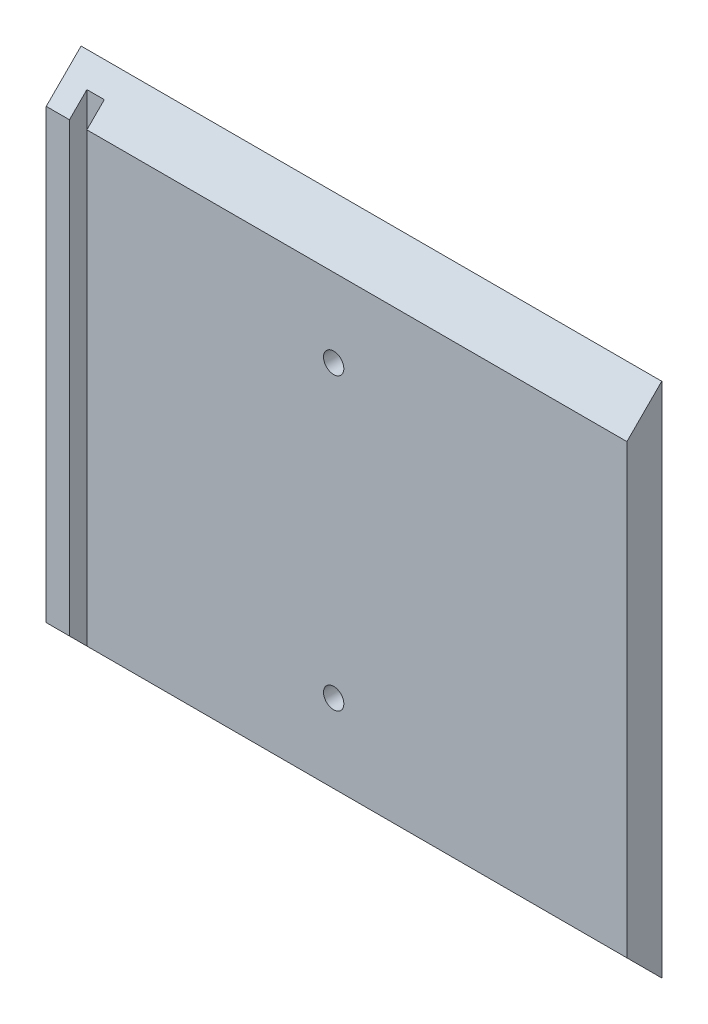
SolidWorks part; units mm, degrees
material "Maple"
ref_plane "Front Plane" through (0, 0, 0) normal (0, 0, 1) x (1, 0, 0)
ref_plane "Top Plane" through (0, 0, 0) normal (0, 1, 0) x (1, 0, 0)
ref_plane "Right Plane" through (0, 0, 0) normal (1, 0, 0) x (0, 0, -1)
sketch "Sketch1" plane through (0, 0, 0) normal (0, 0, 1) x (1, 0, 0)
  line L1 (-50, -44.5) -> (50, -44.5)
  line L2 (-50, -44.5) -> (-50, 44.5)
  line L3 (-50, 44.5) -> (50, 44.5)
  line L4 (50, -44.5) -> (50, 44.5)
  line L5 (-50, -44.5) -> (50, 44.5) construction
  line L6 (-50, 44.5) -> (50, -44.5) construction
  point P0 (0, 0)
  dimension "D1" = 100
  dimension "D2" = 89
extrude "Boss-Extrude1" add sketch "Sketch1" along normal blind 6
chamfer "Chamfer1" distance 6 angle 45 2 edges at (0, -44.5, 6) (0, 44.5, 6)
sketch "Sketch2" plane through (0, 0, 6) normal (0, 0, 1) x (1, 0, 0)
  line L0 (50, 44.5) -> (-50, 44.5) construction
  line L1 (-46, -44.5) -> (-43, -44.5)
  line L2 (-46, -44.5) -> (-46, 44.5)
  line L3 (-46, 44.5) -> (-43, 44.5)
  line L4 (-43, -44.5) -> (-43, 44.5)
  line L5 (-46, -44.5) -> (-43, 44.5) construction
  line L6 (-46, 44.5) -> (-43, -44.5) construction
  line L7 (-50, -44.5) -> (50, -44.5) construction
  line L8 (-50, 38.5) -> (-50, -38.5) construction
  point P0 (-44.5, 0)
  dimension "D1" = 3
  dimension "D2" = 4
extrude "Cut-Extrude1" cut sketch "Sketch2" against normal blind 3
sketch "Sketch3" [suppressed] plane through (0, 0, 0) normal (0, 0, -1) x (-1, 0, 0)
  line L1 (-45, -45) -> (-45, 45) construction
  circle A0 centre (-7, 20) radius 5
  dimension "D3" = 6
  dimension "D1" = 32
  dimension "D2" = 20
extrude "Cut-Extrude2" [suppressed] cut sketch "Sketch3" against normal through all
mirror "Mirror1" [suppressed] about plane through (0, 0, 0) normal (0, 1, 0)
sketch "Sketch4" plane through (0, 0, 0) normal (0, 0, -1) x (-1, 0, 0)
  line L0 (0.5, 25) -> (0.5, -25) construction
  line L1 (-50, 0) -> (50, 0) construction
  line L2 (-50, -44.5) -> (-50, 44.5) construction
  line L3 (50, 44.5) -> (50, -44.5) construction
  circle A0 centre (0.5, 25) radius 1.75
  circle A1 centre (0.5, -25) radius 1.75
  point P10 (0.5, 0)
  dimension "D1" = 3.5
  dimension "D2" = 50
  dimension "D3" = 49.5
extrude "Cut-Extrude3" cut sketch "Sketch4" against normal through all
